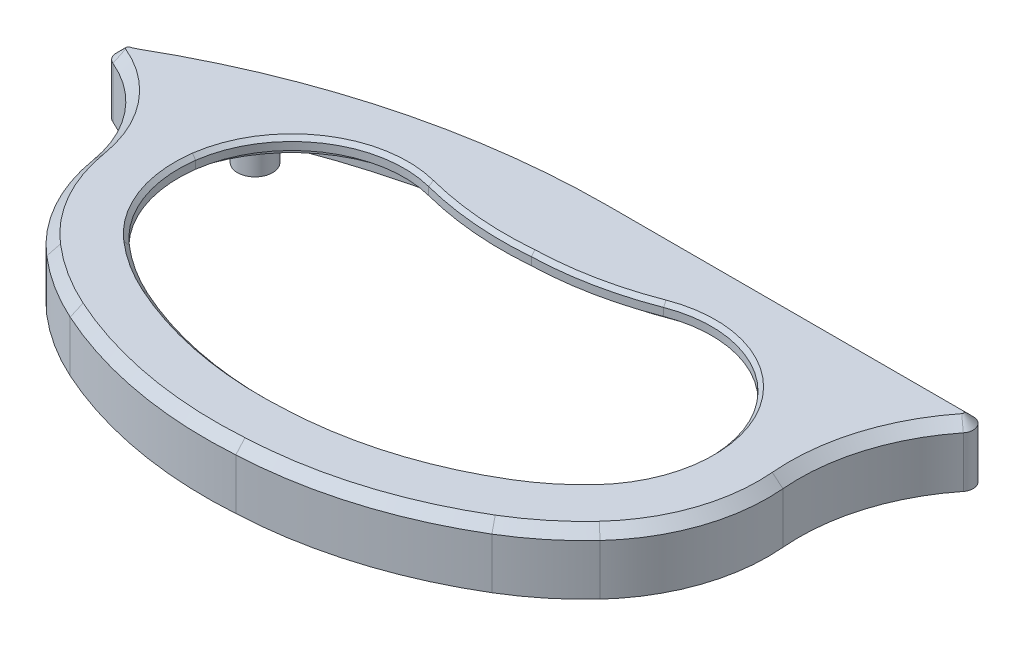
SolidWorks part; units mm, degrees
ref_plane "Front Plane" through (0, 0, 0) normal (0, 0, 1) x (1, 0, 0)
ref_plane "Top Plane" through (0, 0, 0) normal (0, 1, 0) x (1, 0, 0)
ref_plane "Right Plane" through (0, 0, 0) normal (1, 0, 0) x (0, 0, -1)
sketch "Case_Line" plane through (0, 0, 0) normal (0, 1, 0) x (1, 0, 0)
  line L0 (80.0987, 83.4768) -> (-10.614, 83.4768) construction
  arc A0 (85.0987, 88.4768) -> (80.0987, 83.4768) centre (80.0987, 88.4768) cw construction
  arc A2 (-113.6793, 59.6258) -> (-106.8525, 57.7833) centre (-109.3447, 62.1179) ccw construction
  arc A6 (-10.614, 83.4768) -> (-106.8525, 57.7833) centre (-10.614, -109.6066) ccw construction
sketch "Wrest" plane through (0, 0, 0) normal (0, 1, 0) x (1, 0, 0)
  line L6 (-10.569, 65.8598) -> (-6.2316, -9.4162) construction
  line L7 (-10.569, 65.8598) -> (16.1282, 71.2217) construction
  line L8 (16.1282, 71.2217) -> (60.9608, 48.0555) construction
  line L9 (60.9608, 48.0555) -> (52.5888, 15.0143) construction
  line L10 (52.5888, 15.0143) -> (39.5302, 4.389) construction
  line L11 (39.5302, 4.389) -> (-6.2316, -9.4162) construction
  line L14 (80.0987, 83.4768) -> (-10.614, 83.4768) construction
  line L19 (-74.9013, 38.0401) -> (-74.9013, -63.0808) construction
  line L21 (-74.9013, 105.4768) -> (-74.9013, 87.4768) construction
  arc A10 (-10.569, 65.8598) -> (16.1282, 71.2217) centre (-12.89, 146.5605) ccw construction
  arc A11 (16.1282, 71.2217) -> (60.9608, 48.0555) centre (28.2576, 39.7306) cw construction
  arc A12 (60.9608, 48.0555) -> (52.5888, 15.0143) centre (26.348, 39.2445) cw construction
  arc A13 (52.5888, 15.0143) -> (39.5302, 4.389) centre (8.9509, 55.3086) cw construction
  arc A14 (39.5302, 4.389) -> (-6.2316, -9.4162) centre (-10.6307, 87.9151) cw construction
  arc A15 (-53.2763, -0.9584) -> (-6.2316, -9.4162) centre (-13.0408, 87.7763) ccw construction
  arc A16 (-67.4688, 8.0967) -> (-53.2763, -0.9584) centre (-28.7477, 53.1364) ccw construction
  arc A17 (-79.5804, 39.9577) -> (-67.4688, 8.0967) centre (-44.1846, 35.1805) ccw construction
  arc A18 (-37.7053, 68.1198) -> (-79.5804, 39.9577) centre (-46.1374, 35.444) ccw construction
  arc A19 (-10.569, 65.8598) -> (-37.7053, 68.1198) centre (-17.5323, 146.293) cw construction
  arc A20 (12.5339, 80.5534) -> (70.6518, 50.5225) centre (28.2576, 39.7306) cw construction
  arc A24 (-10.2812, 60.8661) -> (17.9253, 66.5558) centre (-12.89, 146.5605) ccw
  arc A50 (70.6518, 50.5225) -> (59.9357, 8.2303) centre (26.348, 39.2445) cw construction
  arc A51 (59.9357, 8.2303) -> (44.6786, -4.1838) centre (8.9509, 55.3086) cw construction
  arc A53 (44.6786, -4.1838) -> (-5.6564, -19.4003) centre (-10.6307, 87.9151) cw construction
  arc A54 (-57.4059, -10.0658) -> (-5.6564, -19.4003) centre (-13.0408, 87.7763) ccw construction
  arc A58 (-73.9879, 0.5138) -> (-57.4059, -10.0658) centre (-28.7477, 53.1364) ccw construction
  arc A71 (17.9253, 66.5558) -> (56.1154, 46.8221) centre (28.2576, 39.7306) cw
  arc A72 (56.1154, 46.8221) -> (48.9153, 18.4063) centre (26.348, 39.2445) cw
  arc A73 (48.9153, 18.4063) -> (36.9561, 8.6755) centre (8.9509, 55.3086) cw
  arc A74 (36.9561, 8.6755) -> (-6.5193, -4.424) centre (-10.6307, 87.9151) cw
  arc A75 (-51.2115, 3.5954) -> (-6.5193, -4.424) centre (-13.0408, 87.7763) ccw
  arc A76 (-64.2092, 11.8882) -> (-51.2115, 3.5954) centre (-28.7477, 53.1364) ccw
  arc A77 (-74.6253, 39.2889) -> (-64.2092, 11.8882) centre (-44.1846, 35.1805) ccw
  arc A78 (-38.9546, 63.2784) -> (-74.6253, 39.2889) centre (-46.1374, 35.444) ccw
  arc A79 (-10.2812, 60.8661) -> (-38.9546, 63.2784) centre (-17.5323, 146.293) cw
  arc A80 (-89.4906, 41.2952) -> (-73.9879, 0.5138) centre (-44.1846, 35.1805) ccw construction
  arc A81 (-35.2066, 77.8026) -> (-89.4906, 41.2952) centre (-46.1374, 35.444) ccw construction
  arc A82 (-11.1445, 75.8479) -> (-35.2066, 77.8026) centre (-17.5323, 146.293) cw construction
  arc A83 (-11.1445, 75.8479) -> (12.5339, 80.5534) centre (-12.89, 146.5605) ccw construction
  arc A85 (-10.614, 83.4768) -> (-106.8525, 57.7833) centre (-10.614, -109.6066) ccw construction
  dimension "D2" = 27.2303
  dimension "D7" = 80.7341
  dimension "D15" = 5
  dimension "D1" = 75.4008
  dimension "D3" = 50.4642
  dimension "D4" = 34.0854
  dimension "D5" = 47.7989
  dimension "D6" = 16.8352
  dimension "D8" = 103.108
  dimension "D9" = 98.059
  dimension "D10" = 76.51
  dimension "D11" = 10
sketch "Sketch6" plane through (0, 0, 0) normal (0, 1, 0) x (1, 0, 0)
  line L0 (84.9594, 87.3051) -> (70.7917, 28.5311) construction
  line L1 (-88.1859, 17.3185) -> (-113.6272, 59.5372) construction
  line L2 (80.0987, 83.4768) -> (-10.614, 83.4768)
  arc A0 (-73.9879, 0.5138) -> (-57.4059, -10.0658) centre (-28.7477, 53.1364) ccw construction
  arc A1 (59.9357, 8.2303) -> (70.6518, 50.5225) centre (26.348, 39.2445) ccw construction
  arc A2 (-113.6793, 59.6258) -> (-106.8525, 57.7833) centre (-109.3447, 62.1179) ccw construction
  arc A3 (80.0987, 83.4768) -> (85.0987, 88.4768) centre (80.0987, 88.4768) ccw construction
  arc A4 (80.1793, 83.4775) -> (82.5748, 78.6094) centre (80.2278, 80.4779) cw
  arc A5 (-107.9166, 57.3262) -> (-108.2193, 51.6843) centre (-107.0597, 54.4512) ccw
  circle A6 centre (80.2278, 80.4779) radius 3 construction
  arc A7 (-5.6564, -19.4003) -> (44.6786, -4.1838) centre (-10.6307, 87.9151) ccw construction
  arc A8 (59.9357, 8.2303) -> (71.8718, 43.1263) centre (26.4104, 39.1869) ccw
  arc A9 (82.5748, 78.6094) -> (71.8718, 43.1263) centre (121.7206, 47.4458) ccw
  circle A10 centre (-107.0597, 54.4512) radius 3 construction
  arc A11 (-57.4059, -10.0658) -> (-5.6564, -19.4003) centre (-13.0408, 87.7763) ccw construction
  arc A12 (-108.2193, 51.6843) -> (-89.2905, 27.7324) centre (-120.4115, 22.5936) cw
  arc A13 (-89.4906, 41.2952) -> (-73.9879, 0.5138) centre (-44.1846, 35.1805) ccw construction
  arc A14 (-73.9879, 0.5138) -> (-89.2905, 27.7324) centre (-44.1846, 35.1805) cw
  arc A15 (-73.9879, 0.5138) -> (-57.4059, -10.0658) centre (-28.7477, 53.1364) ccw
  arc A16 (80.1793, 83.4775) -> (80.0987, 83.4768) centre (80.0987, 88.4768) cw
  arc A21 (-57.4059, -10.0658) -> (-5.6564, -19.4003) centre (-13.0408, 87.7763) ccw
  arc A22 (59.9357, 8.2303) -> (44.6786, -4.1838) centre (8.9509, 55.3086) cw
  arc A23 (44.6786, -4.1838) -> (-5.6564, -19.4003) centre (-10.6307, 87.9151) cw
  arc A24 (70.6518, 50.5225) -> (12.5339, 80.5534) centre (28.2576, 39.7306) ccw construction
  arc A25 (-107.9166, 57.3262) -> (-106.8525, 57.7833) centre (-109.3447, 62.1179) ccw
  arc A26 (-106.8525, 57.7833) -> (-10.614, 83.4768) centre (-10.614, -109.6066) cw
  dimension "D1" = 3
extrude "Top_plane" add sketch "Sketch6" against normal blind 3
sketch "Sketch9" plane through (0, 0, 0) normal (0, 1, 0) x (1, 0, 0)
  arc A20 (-10.2812, 60.8661) -> (17.9253, 66.5558) centre (-12.89, 146.5605) ccw
  arc A21 (56.1154, 46.8221) -> (17.9253, 66.5558) centre (28.2576, 39.7306) ccw
  arc A22 (48.9153, 18.4063) -> (56.1154, 46.8221) centre (26.348, 39.2445) ccw
  arc A23 (36.9561, 8.6755) -> (48.9153, 18.4063) centre (8.9509, 55.3086) ccw
  arc A24 (-6.5193, -4.424) -> (36.9561, 8.6755) centre (-10.6307, 87.9151) ccw
  arc A25 (-51.2115, 3.5954) -> (-6.5193, -4.424) centre (-13.0408, 87.7763) ccw
  arc A26 (-64.2092, 11.8882) -> (-51.2115, 3.5954) centre (-28.7477, 53.1364) ccw
  arc A27 (-74.6253, 39.2889) -> (-64.2092, 11.8882) centre (-44.1846, 35.1805) ccw
  arc A28 (-38.9546, 63.2784) -> (-74.6253, 39.2889) centre (-46.1374, 35.444) ccw
  arc A29 (-38.9546, 63.2784) -> (-10.2812, 60.8661) centre (-17.5323, 146.293) ccw
  arc A30 (-10.2812, 60.8661) -> (17.9253, 66.5558) centre (-12.89, 146.5605) ccw
  arc A31 (56.1154, 46.8221) -> (17.9253, 66.5558) centre (28.2576, 39.7306) ccw
  arc A32 (48.9153, 18.4063) -> (56.1154, 46.8221) centre (26.348, 39.2445) ccw
  arc A33 (36.9561, 8.6755) -> (48.9153, 18.4063) centre (8.9509, 55.3086) ccw
  arc A34 (-6.5193, -4.424) -> (36.9561, 8.6755) centre (-10.6307, 87.9151) ccw
  arc A35 (-51.2115, 3.5954) -> (-6.5193, -4.424) centre (-13.0408, 87.7763) ccw
  arc A36 (-64.2092, 11.8882) -> (-51.2115, 3.5954) centre (-28.7477, 53.1364) ccw
  arc A37 (-74.6253, 39.2889) -> (-64.2092, 11.8882) centre (-44.1846, 35.1805) ccw
  arc A38 (-38.9546, 63.2784) -> (-74.6253, 39.2889) centre (-46.1374, 35.444) ccw
  arc A39 (-38.9546, 63.2784) -> (-10.2812, 60.8661) centre (-17.5323, 146.293) ccw
  dimension "D1" = 0
extrude "Pillow_hole" cut sketch "Sketch9" against normal through all
chamfer "Pillow_chamfer" distance 1 angle 45 10 edges at (16.0353, 0, 0.5854) (43.2822, 0, -13.115) (56.1237, 0, -31.6999) (4.0625, 0, -62.5191) (41.4538, 0, -65.2689) (-29.3655, 0, 3.2014) (-58.0057, 0, -7.2789) (-24.7198, 0, -60.8607) (-72.8968, 0, -24.2659) (-62.1796, 0, -59.2977)
sketch "Sketch7" plane through (0, -3, 0) normal (0, -1, 0) x (1, 0, 0)
  line L3 (-10.614, -83.4768) -> (80.0987, -83.4768)
  line L4 (-10.614, -83.4768) -> (80.0987, -83.4768)
  arc A37 (-106.8525, -57.7833) -> (-10.614, -83.4768) centre (-10.614, 109.6066) ccw
  arc A38 (-106.8525, -57.7833) -> (-107.9166, -57.3262) centre (-109.3447, -62.1179) ccw
  arc A39 (-108.2193, -51.6843) -> (-107.9166, -57.3262) centre (-107.0597, -54.4512) ccw
  arc A40 (-108.2193, -51.6843) -> (-89.2905, -27.7324) centre (-120.4115, -22.5936) ccw
  arc A41 (-73.9879, -0.5138) -> (-89.2905, -27.7324) centre (-44.1846, -35.1805) ccw
  arc A42 (-57.4059, 10.0658) -> (-73.9879, -0.5138) centre (-28.7477, -53.1364) ccw
  arc A43 (-5.6564, 19.4003) -> (-57.4059, 10.0658) centre (-13.0408, -87.7763) ccw
  arc A44 (44.6786, 4.1838) -> (-5.6564, 19.4003) centre (-10.6307, -87.9151) ccw
  arc A45 (59.9357, -8.2303) -> (44.6786, 4.1838) centre (8.9509, -55.3086) ccw
  arc A46 (71.8718, -43.1263) -> (59.9357, -8.2303) centre (26.4104, -39.1869) ccw
  arc A47 (71.8718, -43.1263) -> (82.5748, -78.6094) centre (121.7206, -47.4458) ccw
  arc A48 (80.1793, -83.4775) -> (82.5748, -78.6094) centre (80.2278, -80.4779) ccw
  arc A49 (80.1793, -83.4775) -> (80.0987, -83.4768) centre (80.0987, -88.4768) ccw
  arc A50 (-106.8525, -57.7833) -> (-10.614, -83.4768) centre (-10.614, 109.6066) ccw
  arc A51 (-106.8525, -57.7833) -> (-107.9166, -57.3262) centre (-109.3447, -62.1179) ccw
  arc A52 (-108.2193, -51.6843) -> (-107.9166, -57.3262) centre (-107.0597, -54.4512) ccw
  arc A53 (-108.2193, -51.6843) -> (-89.2905, -27.7324) centre (-120.4115, -22.5936) ccw
  arc A54 (-73.9879, -0.5138) -> (-89.2905, -27.7324) centre (-44.1846, -35.1805) ccw
  arc A55 (-57.4059, 10.0658) -> (-73.9879, -0.5138) centre (-28.7477, -53.1364) ccw
  arc A56 (-5.6564, 19.4003) -> (-57.4059, 10.0658) centre (-13.0408, -87.7763) ccw
  arc A57 (44.6786, 4.1838) -> (-5.6564, 19.4003) centre (-10.6307, -87.9151) ccw
  arc A58 (59.9357, -8.2303) -> (44.6786, 4.1838) centre (8.9509, -55.3086) ccw
  arc A59 (71.8718, -43.1263) -> (59.9357, -8.2303) centre (26.4104, -39.1869) ccw
  arc A60 (71.8718, -43.1263) -> (82.5748, -78.6094) centre (121.7206, -47.4458) ccw
  arc A61 (80.1793, -83.4775) -> (82.5748, -78.6094) centre (80.2278, -80.4779) ccw
  arc A62 (80.1793, -83.4775) -> (80.0987, -83.4768) centre (80.0987, -88.4768) ccw
  arc A188 (-53.2763, 0.9584) -> (-67.4688, -8.0967) centre (-28.7477, -53.1364) ccw
  arc A189 (-6.2316, 9.4162) -> (-53.2763, 0.9584) centre (-13.0408, -87.7763) ccw
  arc A190 (39.5302, -4.389) -> (-6.2316, 9.4162) centre (-10.6307, -87.9151) ccw
  arc A191 (52.5888, -15.0143) -> (39.5302, -4.389) centre (8.9509, -55.3086) ccw
  arc A192 (60.9608, -48.0555) -> (52.5888, -15.0143) centre (26.348, -39.2445) ccw
  arc A193 (16.1282, -71.2217) -> (60.9608, -48.0555) centre (28.2576, -39.7306) ccw
  arc A194 (16.1282, -71.2217) -> (-10.569, -65.8598) centre (-12.89, -146.5605) ccw
  arc A195 (-10.569, -65.8598) -> (-37.7053, -68.1198) centre (-17.5323, -146.293) ccw
  arc A196 (-79.5804, -39.9577) -> (-37.7053, -68.1198) centre (-46.1374, -35.444) ccw
  arc A197 (-67.4688, -8.0967) -> (-79.5804, -39.9577) centre (-44.1846, -35.1805) ccw
  arc A198 (-53.2763, 0.9584) -> (-67.4688, -8.0967) centre (-28.7477, -53.1364) ccw
  arc A199 (-6.2316, 9.4162) -> (-53.2763, 0.9584) centre (-13.0408, -87.7763) ccw
  arc A200 (39.5302, -4.389) -> (-6.2316, 9.4162) centre (-10.6307, -87.9151) ccw
  arc A201 (52.5888, -15.0143) -> (39.5302, -4.389) centre (8.9509, -55.3086) ccw
  arc A202 (60.9608, -48.0555) -> (52.5888, -15.0143) centre (26.348, -39.2445) ccw
  arc A203 (16.1282, -71.2217) -> (60.9608, -48.0555) centre (28.2576, -39.7306) ccw
  arc A204 (16.1282, -71.2217) -> (-10.569, -65.8598) centre (-12.89, -146.5605) ccw
  arc A205 (-10.569, -65.8598) -> (-37.7053, -68.1198) centre (-17.5323, -146.293) ccw
  arc A206 (-79.5804, -39.9577) -> (-37.7053, -68.1198) centre (-46.1374, -35.444) ccw
  arc A207 (-67.4688, -8.0967) -> (-79.5804, -39.9577) centre (-44.1846, -35.1805) ccw
  dimension "D1" = 0
  dimension "D2" = 0
extrude "Wrest_socket" add sketch "Sketch7" along normal blind 4
sketch "Sketch8" plane through (0, -7, 0) normal (0, -1, 0) x (1, 0, 0)
  line L2 (-10.614, -81.4768) -> (80.0987, -81.4768)
  line L6 (-10.614, -83.4768) -> (80.0987, -83.4768)
  line L7 (-10.614, -83.4768) -> (80.0987, -83.4768)
  arc A45 (80.2116, -81.4778) -> (80.0987, -81.4768) centre (80.0987, -88.4768) ccw
  arc A46 (80.2116, -81.4778) -> (81.0101, -79.8551) centre (80.2278, -80.4779) ccw
  arc A47 (69.8793, -42.9536) -> (81.0101, -79.8551) centre (121.7206, -47.4458) ccw
  arc A48 (69.8793, -42.9536) -> (58.4664, -9.5871) centre (26.4104, -39.1869) ccw
  arc A49 (58.4664, -9.5871) -> (43.6489, 2.4693) centre (8.9509, -55.3086) ccw
  arc A50 (43.6489, 2.4693) -> (-5.7714, 17.4035) centre (-10.6307, -87.9151) ccw
  arc A51 (-5.7714, 17.4035) -> (-56.58, 8.2443) centre (-13.0408, -87.7763) ccw
  arc A52 (-56.58, 8.2443) -> (-72.6841, -2.0304) centre (-28.7477, -53.1364) ccw
  arc A53 (-72.6841, -2.0304) -> (-87.3173, -28.0582) centre (-44.1846, -35.1805) ccw
  arc A54 (-107.4463, -53.5289) -> (-87.3173, -28.0582) centre (-120.4115, -22.5936) ccw
  arc A55 (-107.4463, -53.5289) -> (-107.3453, -55.4095) centre (-107.0597, -54.4512) ccw
  arc A56 (-105.8557, -56.0494) -> (-107.3453, -55.4095) centre (-109.3447, -62.1179) ccw
  arc A57 (-105.8557, -56.0494) -> (-10.614, -81.4768) centre (-10.614, 109.6066) ccw
  arc A58 (-106.8525, -57.7833) -> (-10.614, -83.4768) centre (-10.614, 109.6066) ccw
  arc A59 (-106.8525, -57.7833) -> (-107.9166, -57.3262) centre (-109.3447, -62.1179) ccw
  arc A60 (-108.2193, -51.6843) -> (-107.9166, -57.3262) centre (-107.0597, -54.4512) ccw
  arc A61 (-108.2193, -51.6843) -> (-89.2905, -27.7324) centre (-120.4115, -22.5936) ccw
  arc A62 (-73.9879, -0.5138) -> (-89.2905, -27.7324) centre (-44.1846, -35.1805) ccw
  arc A63 (-57.4059, 10.0658) -> (-73.9879, -0.5138) centre (-28.7477, -53.1364) ccw
  arc A64 (-5.6564, 19.4003) -> (-57.4059, 10.0658) centre (-13.0408, -87.7763) ccw
  arc A65 (44.6786, 4.1838) -> (-5.6564, 19.4003) centre (-10.6307, -87.9151) ccw
  arc A66 (59.9357, -8.2303) -> (44.6786, 4.1838) centre (8.9509, -55.3086) ccw
  arc A67 (71.8718, -43.1263) -> (59.9357, -8.2303) centre (26.4104, -39.1869) ccw
  arc A68 (71.8718, -43.1263) -> (82.5748, -78.6094) centre (121.7206, -47.4458) ccw
  arc A69 (80.1793, -83.4775) -> (82.5748, -78.6094) centre (80.2278, -80.4779) ccw
  arc A70 (80.1793, -83.4775) -> (80.0987, -83.4768) centre (80.0987, -88.4768) ccw
  arc A71 (-106.8525, -57.7833) -> (-10.614, -83.4768) centre (-10.614, 109.6066) ccw
  arc A72 (-106.8525, -57.7833) -> (-107.9166, -57.3262) centre (-109.3447, -62.1179) ccw
  arc A73 (-108.2193, -51.6843) -> (-107.9166, -57.3262) centre (-107.0597, -54.4512) ccw
  arc A74 (-108.2193, -51.6843) -> (-89.2905, -27.7324) centre (-120.4115, -22.5936) ccw
  arc A75 (-73.9879, -0.5138) -> (-89.2905, -27.7324) centre (-44.1846, -35.1805) ccw
  arc A76 (-57.4059, 10.0658) -> (-73.9879, -0.5138) centre (-28.7477, -53.1364) ccw
  arc A77 (-5.6564, 19.4003) -> (-57.4059, 10.0658) centre (-13.0408, -87.7763) ccw
  arc A78 (44.6786, 4.1838) -> (-5.6564, 19.4003) centre (-10.6307, -87.9151) ccw
  arc A79 (59.9357, -8.2303) -> (44.6786, 4.1838) centre (8.9509, -55.3086) ccw
  arc A80 (71.8718, -43.1263) -> (59.9357, -8.2303) centre (26.4104, -39.1869) ccw
  arc A81 (71.8718, -43.1263) -> (82.5748, -78.6094) centre (121.7206, -47.4458) ccw
  arc A82 (80.1793, -83.4775) -> (82.5748, -78.6094) centre (80.2278, -80.4779) ccw
  arc A83 (80.1793, -83.4775) -> (80.0987, -83.4768) centre (80.0987, -88.4768) ccw
  dimension "D1" = 0
  dimension "D2" = 2
extrude "Wall" add sketch "Sketch8" along normal blind 8.5
chamfer "Main_chamfer" distance 2.5 angle 45 14 edges at (-110.0554, 0, -54.6119) (-32.1111, 0, 17.9482) (20.4565, 0, 14.9193) (52.7492, 0, -1.4799) (82.9195, 0, -81.8024) (80.139, 0, -83.477) (34.7423, 0, -83.4768) (-95.6642, 0, -42.1509) (-84.0351, 0, -12.7761) (-66.0737, 0, 5.3665) (69.5863, 0, -24.4187) (73.8168, 0, -61.8954) (-60.4187, 0, -76.9429) (-107.3713, 0, -57.5238)
sketch "Sketch10" plane through (0, -7, 0) normal (0, -1, 0) x (1, 0, 0)
  line L0 (-10.2812, -60.8661) -> (-6.5193, 4.424) construction
  line L1 (-78, -57.8598) -> (-8.4002, -28.221) construction
  line L2 (-8.4002, -28.221) -> (47.5551, -4.3927) construction
  circle A0 centre (-78, -57.8598) radius 4.5
  circle A1 centre (-78, -57.8598) radius 1.35
  circle A2 centre (47.5551, -4.3927) radius 4.5
  circle A3 centre (47.5551, -4.3927) radius 1.35
  arc A5 (52.5888, -15.0143) -> (39.5302, -4.389) centre (8.9509, -55.3086) ccw construction
  dimension "D1" = 9
  dimension "D2" = 2.7
  dimension "D3" = 78
  dimension "D4" = 8
extrude "Boss-Extrude1" add sketch "Sketch10" along normal blind 5.5
sketch "Sketch13" plane through (0, -12.5, 0) normal (0, -1, 0) x (1, 0, 0)
  line L1 (-76.4989, -60.4598) -> (-74.9978, -57.8598)
  line L2 (-74.9978, -57.8598) -> (-76.4989, -55.2598)
  line L3 (-76.4989, -55.2598) -> (-79.5011, -55.2598)
  line L4 (-79.5011, -55.2598) -> (-81.0022, -57.8598)
  line L5 (-81.0022, -57.8598) -> (-79.5011, -60.4598)
  line L6 (-79.5011, -60.4598) -> (-76.4989, -60.4598)
  line L7 (49.0562, -6.9927) -> (50.5573, -4.3927)
  line L8 (50.5573, -4.3927) -> (49.0562, -1.7927)
  line L9 (49.0562, -1.7927) -> (46.054, -1.7927)
  line L10 (46.054, -1.7927) -> (44.5529, -4.3927)
  line L11 (44.5529, -4.3927) -> (46.054, -6.9927)
  line L12 (46.054, -6.9927) -> (49.0562, -6.9927)
  circle A0 centre (-78, -57.8598) radius 2.6 construction
  circle A1 centre (47.5551, -4.3927) radius 2.6 construction
  dimension "D1" = 5.2
extrude "Nut_holes" cut sketch "Sketch13" against normal blind 3
ref_plane "Magnet01-Plane1" through (-51.514, 0, -89.5994) normal (-0.4984, 0, -0.8669) x (-0.8669, 0, 0.4984)
ref_plane "Magnet01-Plane2" through (-50.5171, 0, -87.8656) normal (0.4984, 0, 0.8669) x (0.8669, 0, -0.4984)
sketch "Sketch11" plane through (-50.5171, 0, -87.8656) normal (0.4984, 0, 0.8669) x (0.8669, 0, -0.4984)
  line L0 (-63.8328, -15.5) -> (-63.8328, -2.5) construction
  line L2 (-63.8328, -15.5) -> (32.4057, -15.5) construction
  circle A0 centre (-53.8328, -7.5) radius 3
  dimension "D3" = 6
  dimension "D1" = 10
  dimension "D2" = 8
extrude "Magnet01" cut sketch "Sketch11" along normal blind 2 contours A0
sketch "Sketch12" plane through (0, 0, -81.4768) normal (0, 0, -1) x (-1, 0, 0)
  line L1 (-80.0987, -15.5) -> (-80.0987, -2.5) construction
  line L2 (10.614, -15.5) -> (-80.0987, -15.5) construction
  circle A0 centre (-70.0987, -7.5) radius 3
  dimension "D1" = 6
  dimension "D2" = 8
  dimension "D3" = 10
extrude "Magnet02" cut sketch "Sketch12" against normal blind 2
